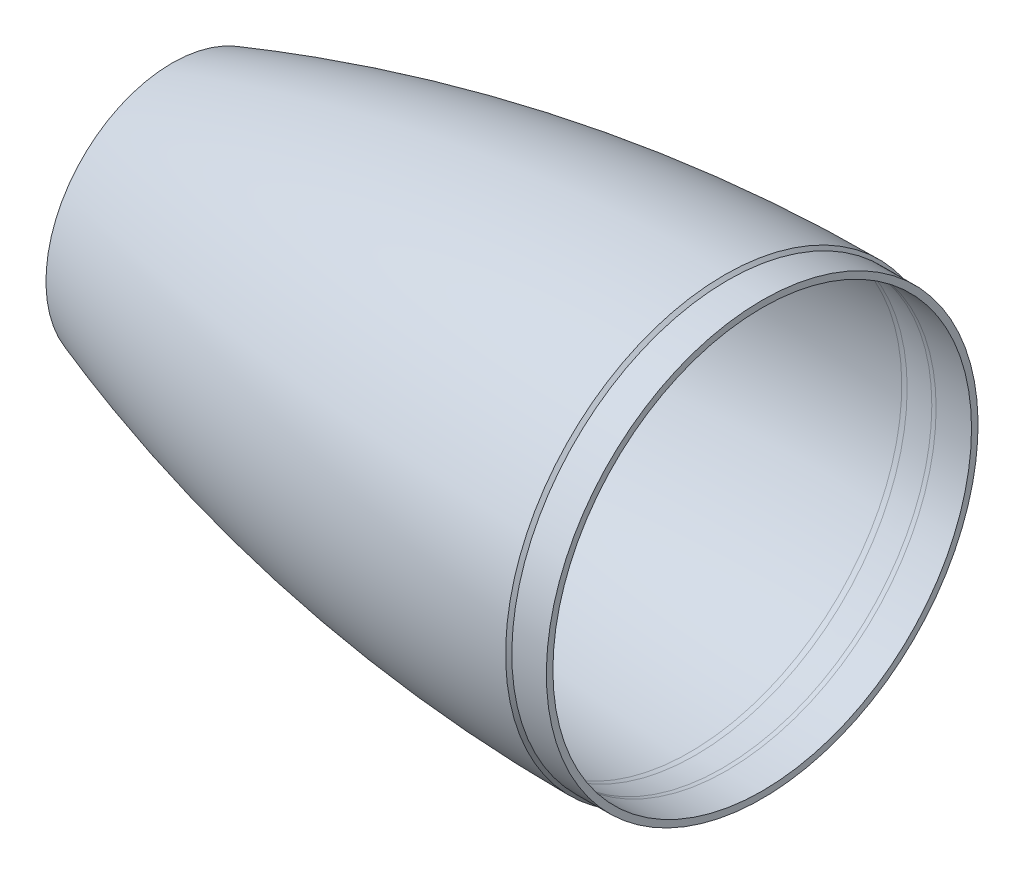
SolidWorks part; units mm, degrees
ref_plane "Front Plane" through (0, 0, 0) normal (0, 0, 1) x (1, 0, 0)
ref_plane "Top Plane" through (0, 0, 0) normal (0, 1, 0) x (1, 0, 0)
ref_plane "Right Plane" through (0, 0, 0) normal (1, 0, 0) x (0, 0, -1)
sketch "Sketch1" plane through (0, 0, 0) normal (0, 0, 1) x (1, 0, 0)
  line L4 (0, 0) -> (-304.8, 0) construction
  line L9 (0, 76.975) -> (0, 0) construction
  line L10 (0, 80.518) -> (50.8, 80.518) construction
  line L11 (-203.2, 46.355) -> (-203.2, 41.4655)
  line L12 (-203.2, 41.4655) -> (-183.7546, 41.4655)
  line L13 (-172.9054, 44.8567) -> (-157.1747, 55.7557)
  line L15 (1.143, 79.375) -> (13.843, 79.375)
  line L16 (0, 80.518) -> (1.143, 79.375)
  line L17 (0.8317, 76.975) -> (13.843, 76.975)
  line L18 (13.843, 76.975) -> (13.843, 79.375)
  line L19 (-0.8286, 77.0475) -> (-10.7651, 77.9168)
  arc A4 (0, 80.518) -> (-203.2, 46.355) centre (0, -540.8758) ccw
  arc A5 (-12.82, 77.9852) -> (-146.6129, 60.5043) centre (0, -540.8758) ccw
  arc A6 (0, 78.118) -> (-202.4152, 44.0869) centre (0, -540.8758) ccw construction
  arc A7 (-172.9054, 44.8567) -> (-183.7546, 41.4655) centre (-183.7546, 60.5155) cw
  arc A8 (-157.1747, 55.7557) -> (-146.6129, 60.5043) centre (-139.0927, 29.6577) cw
  arc A9 (-10.7651, 77.9168) -> (-12.82, 77.9852) centre (-12.4254, 58.9393) ccw
  arc A10 (-0.8286, 77.0475) -> (0.8317, 76.975) centre (0.8317, 96.025) ccw
  point P8 (-57.2734, -19.8104)
  point P9 (0, 313.4439)
  point P10 (-150.9565, 274.6984)
  point P21 (-177.8, 41.4655)
  point P24 (-152.4, 59.0638)
  dimension "D7" = 25.4
  dimension "D10" = 19.05
  dimension "D11" = 31.75
  dimension "D17" = 19.05
  dimension "D1" = 161.036
  dimension "D2" = 50.8
  dimension "D3" = 203.2
  dimension "D4" = 92.71
  dimension "D6" = 82.931
  dimension "D8" = 25.4
  dimension "D9" = 304.8
  dimension "D12" = 12.7
  dimension "D13" = 158.75
  dimension "D14" = 45
  dimension "D15" = 2.4
  dimension "D16" = 175
  dimension "D5" = 2.4
revolve "Revolve1" add sketch "Sketch1" angle 360 about L4
